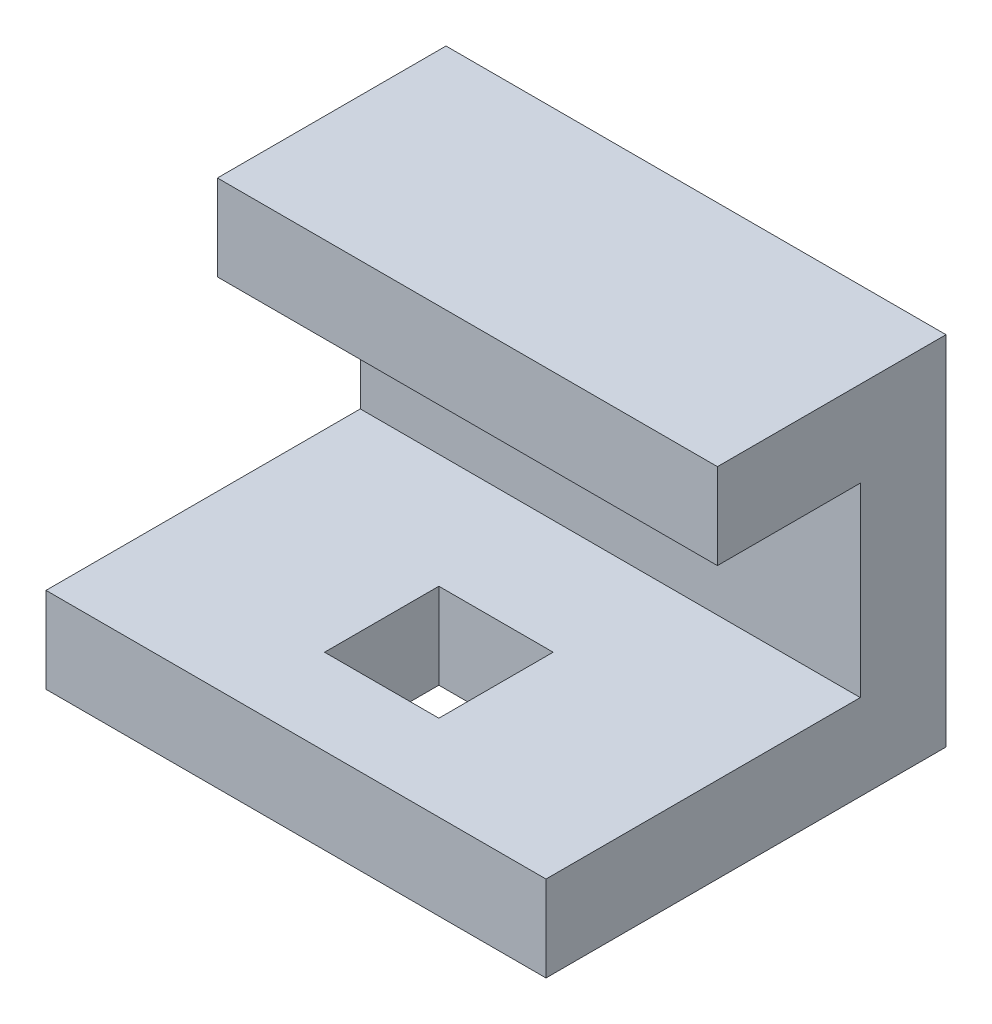
SolidWorks part; units mm, degrees
ref_plane "Plano frontal" through (0, 0, 0) normal (0, 0, 1) x (1, 0, 0)
ref_plane "Plano superior" through (0, 0, 0) normal (0, 1, 0) x (1, 0, 0)
ref_plane "Plano direito" through (0, 0, 0) normal (1, 0, 0) x (0, 0, -1)
sketch "Esboço1" plane through (0, 0, 0) normal (0, 0, 1) x (1, 0, 0)
  line L1 (0, 0) -> (70, 0)
  line L2 (0, 0) -> (0, -50)
  line L3 (0, -50) -> (70, -50)
  line L4 (70, 0) -> (70, -50)
  dimension "D1" = 50
  dimension "D2" = 70
extrude "Ressalto-extrusão1" add sketch "Esboço1" along normal blind 56
sketch "Esboço2" plane through (0, 0, 0) normal (-1, 0, 0) x (0, 0, 1)
  line L10 (56, 0) -> (56, -50) construction
  line L11 (12, -38) -> (56, -38)
  line L12 (12, -38) -> (12, -12)
  line L13 (12, -12) -> (56, -12)
  line L14 (56, -38) -> (56, -12)
  line M14 (56, -50) -> (56, 0)
extrude "Corte-extrusão2" cut sketch "Esboço2" against normal blind 70 contours L13 L12 L11 M14 region at (0, -25, 34)
sketch "Esboço3" plane through (0, 0, 0) normal (-1, 0, 0) x (0, 0, 1)
  line L1 (32, -12) -> (56, -12)
  line L2 (32, -12) -> (32, 0)
  line L3 (32, 0) -> (56, 0)
  line L4 (56, -12) -> (56, 0)
  dimension "D1" = 32
  dimension "D2" = 12
sketch "Esboço4" plane through (0, -38, 0) normal (0, 1, 0) x (1, 0, 0)
  line L0 (0, -56) -> (27, -56)
  line L1 (0, -56) -> (70, -56) construction
  line L2 (27, -56) -> (43, -56)
  line L3 (27, -56) -> (27, -44)
  line L4 (27, -44) -> (27, -28)
  line L6 (27, -28) -> (43, -28)
  line L7 (27, -28) -> (27, -44)
  line L8 (27, -44) -> (43, -44)
  line L9 (43, -28) -> (43, -44)
  dimension "D1" = 27
  dimension "D2" = 16
  dimension "D3" = 12
  dimension "D4" = 16
extrude "Corte-extrusão5" cut sketch "Esboço3" against normal through all
extrude "Corte-extrusão4" cut sketch "Esboço4" against normal blind 70 contours L9 L6 L4 L8 region at (35, -38, 36)
